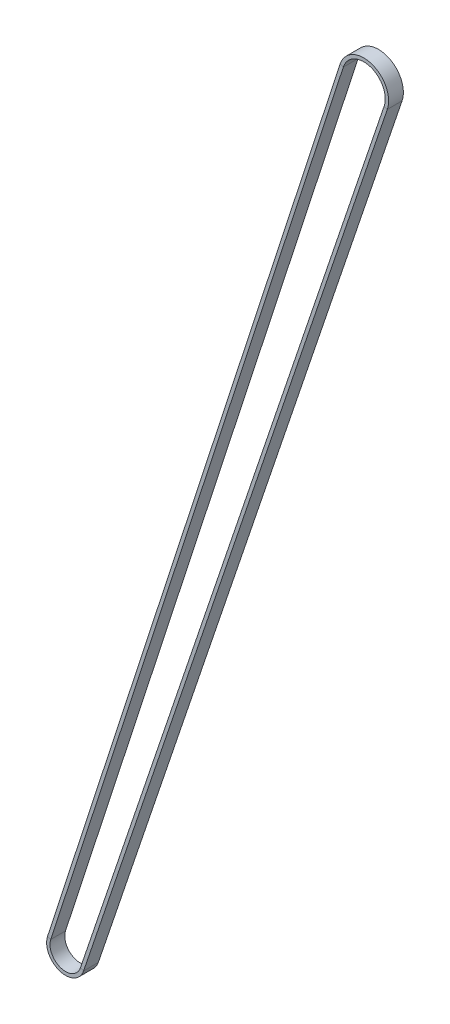
SolidWorks part; units mm, degrees
material "BUTYL"
ref_plane "Front Plane" through (0, 0, 0) normal (0, 0, 1) x (1, 0, 0)
ref_plane "Top Plane" through (0, 0, 0) normal (0, 1, 0) x (1, 0, 0)
ref_plane "Right Plane" through (0, 0, 0) normal (1, 0, 0) x (0, 0, -1)
sketch "Sketch1" plane through (0, 0, 0) normal (0, 0, 1) x (1, 0, 0)
  line L0 (6.0152, -2.0346) -> (129.6722, 363.5599)
  line L1 (-6.0401, 1.9596) -> (113.0606, 369.0636)
  circle A0 centre (0, 0) radius 6.35 construction
  arc A1 (-6.0401, 1.9596) -> (6.0152, -2.0346) centre (0, 0) ccw
  circle A2 centre (121.3835, 366.3634) radius 8.75 construction
  arc A3 (129.6722, 363.5599) -> (113.0606, 369.0636) centre (121.3835, 366.3634) ccw
  point P10 (0, 0)
  point P11 (0, 0)
  point P12 (0, 0)
  point P13 (0, 0)
ref_plane "Plane1" through (113.0606, 369.0636, 0) normal (0.3086, 0.9512, 0) x (0.9512, -0.3086, 0)
sketch "Sketch2" plane through (113.0606, 369.0636, 0) normal (0.3086, 0.9512, 0) x (0.9512, -0.3086, 0)
  line L0 (-1.38, -3) -> (0, -3)
  line L1 (-1.38, -3) -> (-1.38, 3)
  line L2 (0, -3) -> (0, 3)
  line L3 (-1.38, 3) -> (0, 3)
  line L4 (-1.38, -3) -> (0, 3) construction
  line L5 (0, -3) -> (-1.38, 3) construction
  point P0 (-0.7722, -0.4238)
  point P1 (-0.69, 0)
  point P2 (0, 0)
  dimension "D1" = 6
  dimension "D2" = 1.38
sweep "Sweep1" add profiles "Sketch2" path "Sketch1"
